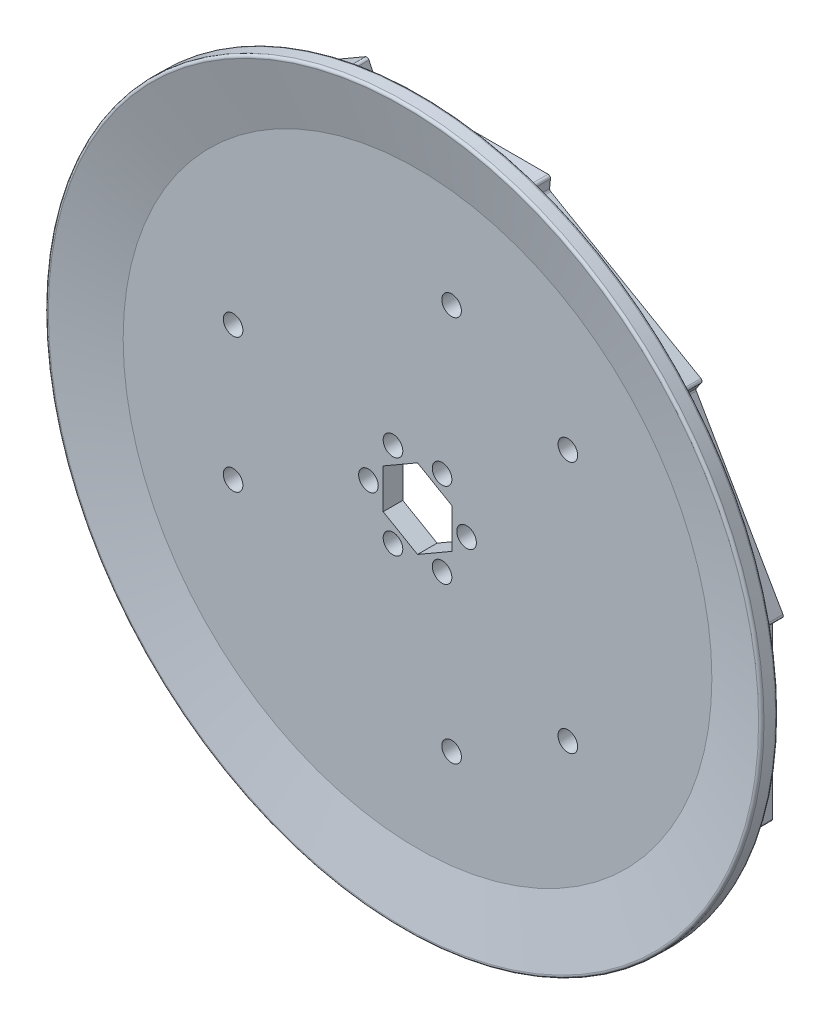
SolidWorks part; units mm, degrees
ref_plane "Front" through (0, 0, 0) normal (0, 0, 1) x (1, 0, 0)
ref_plane "Top" through (0, 0, 0) normal (0, 1, 0) x (1, 0, 0)
ref_plane "Right" through (0, 0, 0) normal (1, 0, 0) x (0, 0, -1)
sketch "Szkic1" plane through (0, 0, 0) normal (0, 0, 1) x (1, 0, 0)
  line L0 (0, 8.0829) -> (7, 4.0415)
  line L1 (-7, -4.0415) -> (-7, 4.0415)
  line L2 (0, -8.0829) -> (-7, -4.0415)
  line L3 (-7, 4.0415) -> (0, 8.0829)
  line L4 (7, -4.0415) -> (0, -8.0829)
  line L5 (7, 4.0415) -> (7, -4.0415)
  line L6 (0, -68.3372) -> (12.6961, -68.3372)
  line L7 (34.1686, -59.1817) -> (14.5884, -70.4864)
  line L8 (34.1686, -59.1817) -> (45.1637, -52.8337)
  line L9 (59.1817, -34.1686) -> (47.8771, -53.7488)
  line L10 (59.1817, -34.1686) -> (65.5298, -23.1735)
  line L11 (68.3372, 0) -> (68.3372, -22.6093)
  line L12 (68.3372, 0) -> (68.3372, 12.6961)
  line L13 (59.1817, 34.1686) -> (70.4864, 14.5884)
  line L14 (59.1817, 34.1686) -> (52.8337, 45.1637)
  line L15 (34.1686, 59.1817) -> (53.7488, 47.8771)
  line L16 (34.1686, 59.1817) -> (23.1735, 65.5298)
  line L17 (0, 68.3372) -> (22.6093, 68.3372)
  line L18 (0, 68.3372) -> (-12.6961, 68.3372)
  line L19 (-34.1686, 59.1817) -> (-14.5884, 70.4864)
  line L20 (-34.1686, 59.1817) -> (-45.1637, 52.8337)
  line L21 (-59.1817, 34.1686) -> (-47.8771, 53.7488)
  line L22 (-59.1817, 34.1686) -> (-65.5298, 23.1735)
  line L23 (-68.3372, 0) -> (-68.3372, 22.6093)
  line L24 (-68.3372, 0) -> (-68.3372, -12.6961)
  line L25 (-59.1817, -34.1686) -> (-70.4864, -14.5884)
  line L26 (-59.1817, -34.1686) -> (-52.8337, -45.1637)
  line L27 (-34.1686, -59.1817) -> (-53.7488, -47.8771)
  line L28 (-34.1686, -59.1817) -> (-23.1735, -65.5298)
  line L29 (0, -68.3372) -> (-22.6093, -68.3372)
  line L30 (-10, 0) -> (10, 0) construction
  line L31 (-5, 8.6603) -> (5, -8.6603) construction
  circle A0 centre (-37.5877, 13.6808) radius 2
  circle A1 centre (30.6418, 25.7115) radius 2
  circle A2 centre (-37.5877, -13.6808) radius 2
  circle A3 centre (6.9459, -39.3923) radius 2
  circle A4 centre (30.6418, -25.7115) radius 2
  circle A5 centre (6.9459, 39.3923) radius 2
  circle A6 centre (5, 8.6603) radius 2
  circle A7 centre (-10, 0) radius 2
  circle A8 centre (5, -8.6603) radius 2
  circle A9 centre (-5, 8.6603) radius 2
  circle A10 centre (-5, -8.6603) radius 2
  circle A11 centre (10, 0) radius 2
  arc A12 (13.8778, -70.248) -> (13.1475, -68.6222) centre (-23, -85.8372) ccw
  arc A13 (13.1475, -68.6222) -> (12.6961, -68.3372) centre (12.6961, -68.8372) ccw
  arc A14 (13.8778, -70.248) -> (14.5884, -70.4864) centre (14.3384, -70.0533) ccw
  arc A15 (47.1426, -53.8976) -> (45.6972, -52.8548) centre (23, -85.8372) ccw
  arc A16 (45.6972, -52.8548) -> (45.1637, -52.8337) centre (45.4137, -53.2667) ccw
  arc A17 (47.1426, -53.8976) -> (47.8771, -53.7488) centre (47.4441, -53.4988) ccw
  arc A18 (67.7755, -23.1054) -> (66.0023, -22.925) centre (62.8372, -62.8372) ccw
  arc A19 (66.0023, -22.925) -> (65.5298, -23.1735) centre (65.9628, -23.4235) ccw
  arc A20 (67.7755, -23.1054) -> (68.3372, -22.6093) centre (67.8372, -22.6093) ccw
  arc A21 (70.248, 13.8778) -> (68.6222, 13.1475) centre (85.8372, -23) ccw
  arc A22 (68.6222, 13.1475) -> (68.3372, 12.6961) centre (68.8372, 12.6961) ccw
  arc A23 (70.248, 13.8778) -> (70.4864, 14.5884) centre (70.0533, 14.3384) ccw
  arc A24 (53.8977, 47.1426) -> (52.8548, 45.6972) centre (85.8372, 23) ccw
  arc A25 (52.8548, 45.6972) -> (52.8337, 45.1637) centre (53.2667, 45.4137) ccw
  arc A26 (53.8977, 47.1426) -> (53.7488, 47.8771) centre (53.4988, 47.4441) ccw
  arc A27 (23.1054, 67.7755) -> (22.925, 66.0023) centre (62.8372, 62.8372) ccw
  arc A28 (22.925, 66.0023) -> (23.1735, 65.5298) centre (23.4235, 65.9628) ccw
  arc A29 (23.1054, 67.7755) -> (22.6093, 68.3372) centre (22.6093, 67.8372) ccw
  arc A30 (-13.8778, 70.248) -> (-13.1475, 68.6222) centre (23, 85.8372) ccw
  arc A31 (-13.1475, 68.6222) -> (-12.6961, 68.3372) centre (-12.6961, 68.8372) ccw
  arc A32 (-13.8778, 70.248) -> (-14.5884, 70.4864) centre (-14.3384, 70.0533) ccw
  arc A33 (-47.1426, 53.8977) -> (-45.6972, 52.8548) centre (-23, 85.8372) ccw
  arc A34 (-45.6972, 52.8548) -> (-45.1637, 52.8337) centre (-45.4137, 53.2667) ccw
  arc A35 (-47.1426, 53.8977) -> (-47.8771, 53.7488) centre (-47.4441, 53.4988) ccw
  arc A36 (-67.7755, 23.1054) -> (-66.0023, 22.925) centre (-62.8372, 62.8372) ccw
  arc A37 (-66.0023, 22.925) -> (-65.5298, 23.1735) centre (-65.9628, 23.4235) ccw
  arc A38 (-67.7755, 23.1054) -> (-68.3372, 22.6093) centre (-67.8372, 22.6093) ccw
  arc A39 (-70.248, -13.8778) -> (-68.6222, -13.1475) centre (-85.8372, 23) ccw
  arc A40 (-68.6222, -13.1475) -> (-68.3372, -12.6961) centre (-68.8372, -12.6961) ccw
  arc A41 (-70.248, -13.8778) -> (-70.4864, -14.5884) centre (-70.0533, -14.3384) ccw
  arc A42 (-53.8977, -47.1426) -> (-52.8548, -45.6972) centre (-85.8372, -23) ccw
  arc A43 (-52.8548, -45.6972) -> (-52.8337, -45.1637) centre (-53.2667, -45.4137) ccw
  arc A44 (-53.8977, -47.1426) -> (-53.7488, -47.8771) centre (-53.4988, -47.4441) ccw
  arc A45 (-23.1054, -67.7755) -> (-22.925, -66.0023) centre (-62.8372, -62.8372) ccw
  arc A46 (-22.925, -66.0023) -> (-23.1735, -65.5298) centre (-23.4235, -65.9628) ccw
  arc A47 (-23.1054, -67.7755) -> (-22.6093, -68.3372) centre (-22.6093, -67.8372) ccw
extrude "Dodanie-wyciągnięcie1" add sketch "Szkic1" along normal blind 4
sketch "Szkic2" plane through (0, 0, 4) normal (0, 0, 1) x (1, 0, 0)
  circle A0 centre (0, 0) radius 60
  circle A1 centre (0, 0) radius 73
  dimension "D1" = 120
  dimension "D2" = 146
extrude "Dodanie-wyciągnięcie2" add sketch "Szkic2" along normal blind 3
sketch "Szkic4" plane through (0, 0, 0) normal (0, 1, 0) x (1, 0, 0)
  line L0 (-60, -4) -> (-73, -7)
  line L1 (73, -4) -> (-73, -4) construction
  line L2 (-73, -7) -> (73, -7) construction
  line L3 (-73, -7) -> (-73, -11.5569)
  line L4 (-73, -11.5569) -> (-60, -11.5569)
  line L5 (-60, -11.5569) -> (-60, -4)
  line L6 (-60, -4) -> (-60, -7) construction
  line L7 (0, 0) -> (0, -30.6727) construction
revolve "Wycięcie-obrót1" cut sketch "Szkic4" angle 360 about L7
sketch "Szkic5" plane through (0, 0, 4) normal (0, 0, -1) x (-1, 0, 0)
  circle A0 centre (0, 0) radius 73
  circle A1 centre (0, 0) radius 60
extrude "Dodanie-wyciągnięcie3" add sketch "Szkic5" along normal blind 0.5
fillet "Zaokrąglenie2" radius 0.5 2 edges at (-73, 0, 7) (-73, 0, 3.5)
